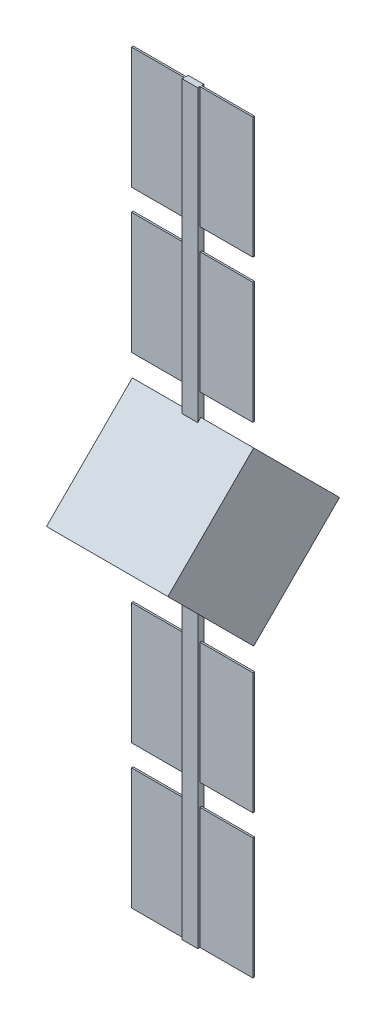
SolidWorks part; units mm, degrees
ref_plane "Piano frontale" through (0, 0, 0) normal (0, 0, 1) x (1, 0, 0)
ref_plane "Piano superiore" through (0, 0, 0) normal (0, 1, 0) x (1, 0, 0)
ref_plane "Piano destro" through (0, 0, 0) normal (1, 0, 0) x (0, 0, -1)
sketch "Schizzo1" plane through (0, 0, 0) normal (0, 1, 0) x (1, 0, 0)
  line L1 (350, -350) -> (-350, -350)
  line L2 (350, -350) -> (350, 350)
  line L3 (350, 350) -> (-350, 350)
  line L4 (-350, -350) -> (-350, 350)
  line L5 (350, -350) -> (-350, 350) construction
  line L6 (350, 350) -> (-350, -350) construction
  point P0 (0, 0)
  dimension "D1" = 700
extrude "Estrusione-Estrusione1" add sketch "Schizzo1" along normal mid plane 700
ref_axis "X axis" through (-713.3024, 0, 0) along (1, 0, 0)
ref_axis "Y axis" through (0, 2411.2521, 0) along (0, -1, 0)
ref_axis "Z axis" through (0, 0, -1120.0626) along (0, 0, 1)
ref_plane "Piano1" through (0, 0, 0) normal (-0.7071, 0, 0.7071) x (0, -1, 0)
ref_plane "Piano2" through (0, 0, 0) normal (0.7071, 0, 0.7071) x (0, -1, 0)
ref_axis "Assiale" through (1589.8132, 0, -1589.8132) along (-0.7071, 0, 0.7071)
sketch "Schizzo4" plane through (0, 0, 0) normal (-0.7071, 0, 0.7071) x (0, -1, 0)
  line L1 (45, 17.5) -> (-45, 17.5)
  line L2 (45, 17.5) -> (45, -17.5)
  line L3 (45, -17.5) -> (-45, -17.5)
  line L4 (-45, 17.5) -> (-45, -17.5)
  line L5 (45, 17.5) -> (-45, -17.5) construction
  line L6 (45, -17.5) -> (-45, 17.5) construction
  point P0 (0, 0)
  dimension "D1" = 90
  dimension "D2" = 35
extrude "Estrusione-Estrusione2" add sketch "Schizzo4" along normal mid plane 4300
sketch "Schizzo6" plane through (0, 0, 0) normal (0.7071, 0, 0.7071) x (0, -1, 0)
  line L0 (0, 2248.3354) -> (0, -2286.6178) construction
  line L1 (350, -624.9747) -> (-350, -624.9747)
  line L2 (350, -624.9747) -> (350, -1324.9747)
  line L3 (350, -1324.9747) -> (-350, -1324.9747)
  line L4 (-350, -624.9747) -> (-350, -1324.9747)
  line L5 (350, -624.9747) -> (-350, -1324.9747) construction
  line L6 (350, -1324.9747) -> (-350, -624.9747) construction
  line L7 (45, -494.9747) -> (350, -494.9747) construction
  point P0 (0, -974.9747)
  dimension "D1" = 700
  dimension "D2" = 130
extrude "Estrusione-Estrusione3" add sketch "Schizzo6" along normal mid plane 10
sketch "Schizzo7" plane through (0, 0, 0) normal (0.7071, 0, 0.7071) x (0, -1, 0)
  line L0 (0, 2248.3354) -> (0, -2286.6178) construction
  line L1 (350, -2150) -> (-350, -2150)
  line L2 (350, -2150) -> (350, -1450)
  line L3 (350, -1450) -> (-350, -1450)
  line L4 (-350, -2150) -> (-350, -1450)
  line L5 (350, -2150) -> (-350, -1450) construction
  line L6 (350, -1450) -> (-350, -2150) construction
  line L7 (350, -1324.9747) -> (350, -624.9747) construction
  line L8 (350, -1324.9747) -> (350, -624.9747) construction
  line L9 (45, -2150) -> (-45, -2150) construction
  point P0 (0, -1800)
extrude "Estrusione-Estrusione4" add sketch "Schizzo7" along normal mid plane 10
mirror "Specchia1" about plane through (0, 0, 0) normal (-0.7071, 0, 0.7071) of "Estrusione-Estrusione4", "Estrusione-Estrusione3"
move or copy body "Corpo-Sposta/copia1" bodies to move or copy 105 copy no rotation origin (0, 0, 0) rotation axis (0.3574, -0.3574, 0.8629) rotation angle 98.421
